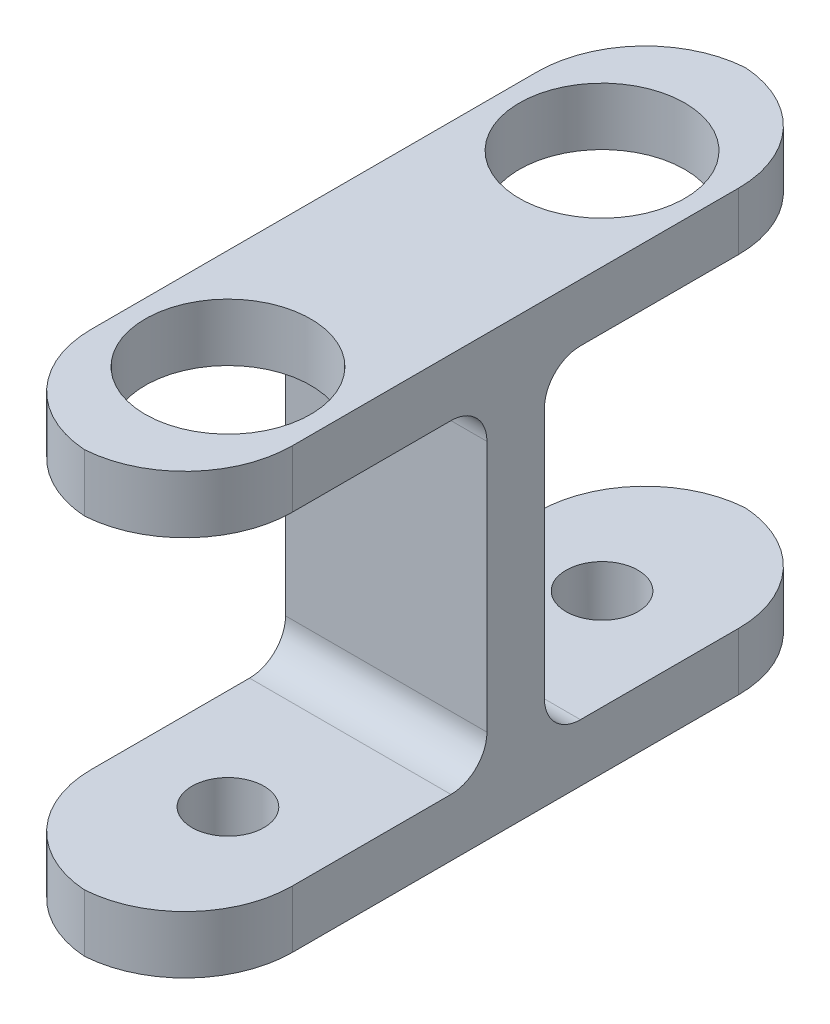
SolidWorks part; units mm, degrees
ref_plane "Front Plane" through (0, 0, 0) normal (0, 0, 1) x (1, 0, 0)
ref_plane "Top Plane" through (0, 0, 0) normal (0, 1, 0) x (1, 0, 0)
ref_plane "Right Plane" through (0, 0, 0) normal (1, 0, 0) x (0, 0, -1)
sketch "Sketch1" plane through (0, 0, 0) normal (1, 0, 0) x (0, 0, -1)
  line L0 (0, 0) -> (42, 0)
  line L1 (42, 0) -> (42, -45)
  line L2 (42, -45) -> (0, -45)
  line L3 (0, -45) -> (0, -53)
  line L4 (0, -53) -> (46, -53)
  line L5 (46, -53) -> (46, 8)
  line L6 (46, 8) -> (0, 8)
  line L7 (0, 8) -> (0, 0)
  dimension "D1" = 42
  dimension "D2" = 45
  dimension "D3" = 8
  dimension "D4" = 4
extrude "Boss-Extrude1" add sketch "Sketch1" along normal blind 28 contours L0 L1 L2 L3 L4 L5 L6 L7
sketch "Sketch2" plane through (0, 8, 0) normal (0, 1, 0) x (1, 0, 0)
  line L0 (28, 0) -> (0, 0) construction
  circle A0 centre (14, 20) radius 11.5
  point P2 (14, 0)
  dimension "D1" = 23
  dimension "D2" = 20
extrude "Cut-Extrude1" cut sketch "Sketch2" against normal up to next
sketch "Sketch3" plane through (0, -45, 0) normal (0, 1, 0) x (1, 0, 0)
  circle A0 centre (14, 20) radius 5
  circle A1 centre (14, 20) radius 11.5 construction
  dimension "D1" = 10
extrude "Cut-Extrude2" cut sketch "Sketch3" against normal up to next contours A0
fillet "Fillet2" radius 5 2 edges at (14, 0, -42) (14, -45, -42)
mirror "Mirror2" about plane through (28, -53, -46) normal (0, 0, 1) of "Fillet2", "Boss-Extrude1", "Cut-Extrude1", "Cut-Extrude2"
fillet "Fillet3" radius 15 8 edges at (28, -49, 0) (0, -49, 0) (28, 4, 0) (0, 4, 0) (0, 4, -92) (0, -49, -92) (28, -49, -92) (28, 4, -92)
